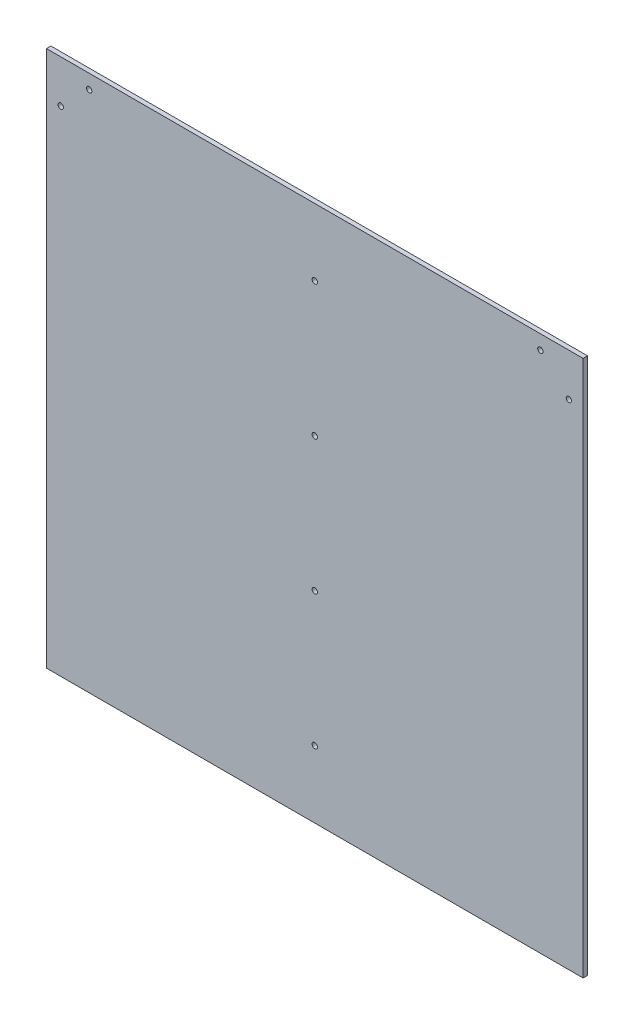
SolidWorks part; units mm, degrees
material "Balsa"
ref_plane "Front Plane" through (0, 0, 0) normal (0, 0, 1) x (1, 0, 0)
ref_plane "Top Plane" through (0, 0, 0) normal (0, 1, 0) x (1, 0, 0)
ref_plane "Right Plane" through (0, 0, 0) normal (1, 0, 0) x (0, 0, -1)
sketch "Sketch1" plane through (0, 0, 0) normal (0, 0, 1) x (1, 0, 0)
  line L1 (173, 396.7) -> (-227, 396.7)
  line L2 (173, 396.7) -> (173, -3.3)
  line L3 (173, -3.3) -> (-227, -3.3)
  line L4 (-227, 396.7) -> (-227, -3.3)
  line L5 (173, 396.7) -> (-227, -3.3) construction
  line L6 (173, -3.3) -> (-227, 396.7) construction
  point P4 (-27, 196.7)
extrude "Boss-Extrude1" add sketch "Sketch1" along normal blind 3.3
sketch "Sketch2" plane through (0, 0, 3.3) normal (0, 0, 1) x (1, 0, 0)
  line L0 (-227, -3.3) -> (173, -3.3) construction
  line L1 (-54, -3.3) -> (0, -3.3)
  line L2 (-54, -3.3) -> (-54, 396.7)
  line L3 (-54, 396.7) -> (0, 396.7)
  line L4 (0, -3.3) -> (0, 396.7)
  line L5 (-54, -3.3) -> (0, 396.7) construction
  line L6 (-54, 396.7) -> (0, -3.3) construction
  line L7 (173, 396.7) -> (-227, 396.7) construction
  line L8 (0, 393.4) -> (0, 0) construction
  line L9 (-54, 393.4) -> (-54, 0) construction
  line L10 (-27, -3.3) -> (-27, 396.7) construction
  line L11 (-54, 196.7) -> (0, 196.7) construction
  line L12 (162.3934, 364.8802) -> (141.1802, 386.0934) construction
  circle A0 centre (-27, 146.7) radius 2
  circle A1 centre (-27, 46.7) radius 2
  circle A2 centre (-27, 246.7) radius 2
  circle A3 centre (-27, 346.7) radius 2
  circle A4 centre (162.3934, 364.8802) radius 2
  circle A5 centre (141.1802, 386.0934) radius 2
  circle A6 centre (-195.1802, 386.0934) radius 2
  circle A7 centre (-216.3934, 364.8802) radius 2
  point P4 (-27, 196.7)
  point P30 (151.7868, 375.4868)
  point P37 (-27, 196.7)
  dimension "D1" = 50
  dimension "D2" = 150
  dimension "D3" = 4
  dimension "D4" = 4
  dimension "D5" = 4
  dimension "D6" = 4
  dimension "D10" = 21.2132
  dimension "D7" = 30
  dimension "D8" = 45
  dimension "D9" = 30
  dimension "D11" = 2
extrude "Cut-Extrude1" cut sketch "Sketch2" against normal blind 4 contours A4 | A5 | A1 | A0 | A2 | A3 | A6 | A7 region at (162.3934, 364.8802, 3.3) region at (141.1802, 386.0934, 3.3)
